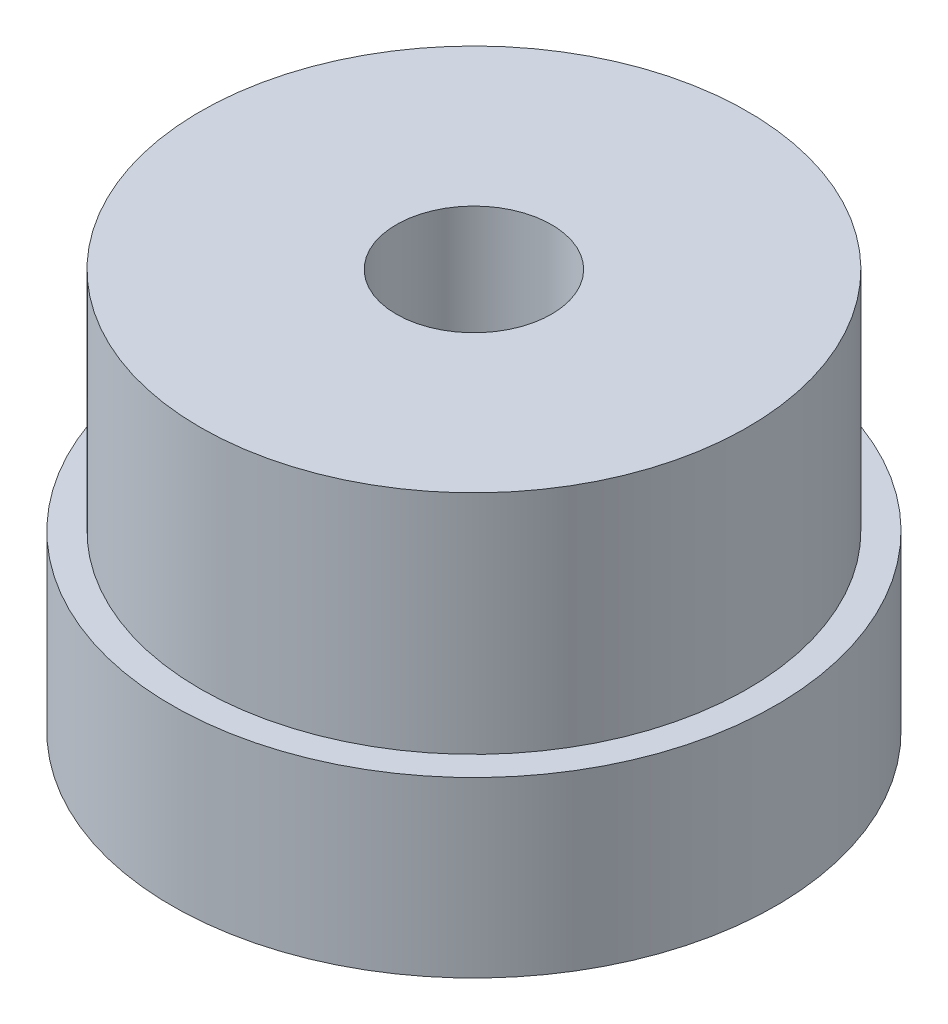
SolidWorks part; units mm, degrees
ref_plane "Front Plane" through (0, 0, 0) normal (0, 0, 1) x (1, 0, 0)
ref_plane "Top Plane" through (0, 0, 0) normal (0, 1, 0) x (1, 0, 0)
ref_plane "Right Plane" through (0, 0, 0) normal (1, 0, 0) x (0, 0, -1)
sketch "Sketch1" plane through (0, 0, 0) normal (0, 1, 0) x (1, 0, 0)
  circle A0 centre (0, 0) radius 11.5062
  circle A1 centre (0, 0) radius 12.7
  circle A2 centre (0, 0) radius 3.2639
  dimension "D1" = 23.0124
  dimension "D2" = 25.4
  dimension "D3" = 6.5278
extrude "Boss-Extrude1" add sketch "Sketch1" along normal blind 16.8275 contours A0 region at (-11.1808, 0, 0)
extrude "Boss-Extrude2" add sketch "Sketch1<3>" along normal blind 7.3025 contours A1 A0 region at (-12.3408, 0, 0)
sketch "Sketch1<3>" plane through (0, 0, 0) normal (0, 1, 0) x (1, 0, 0) same geometry as "Sketch1"
